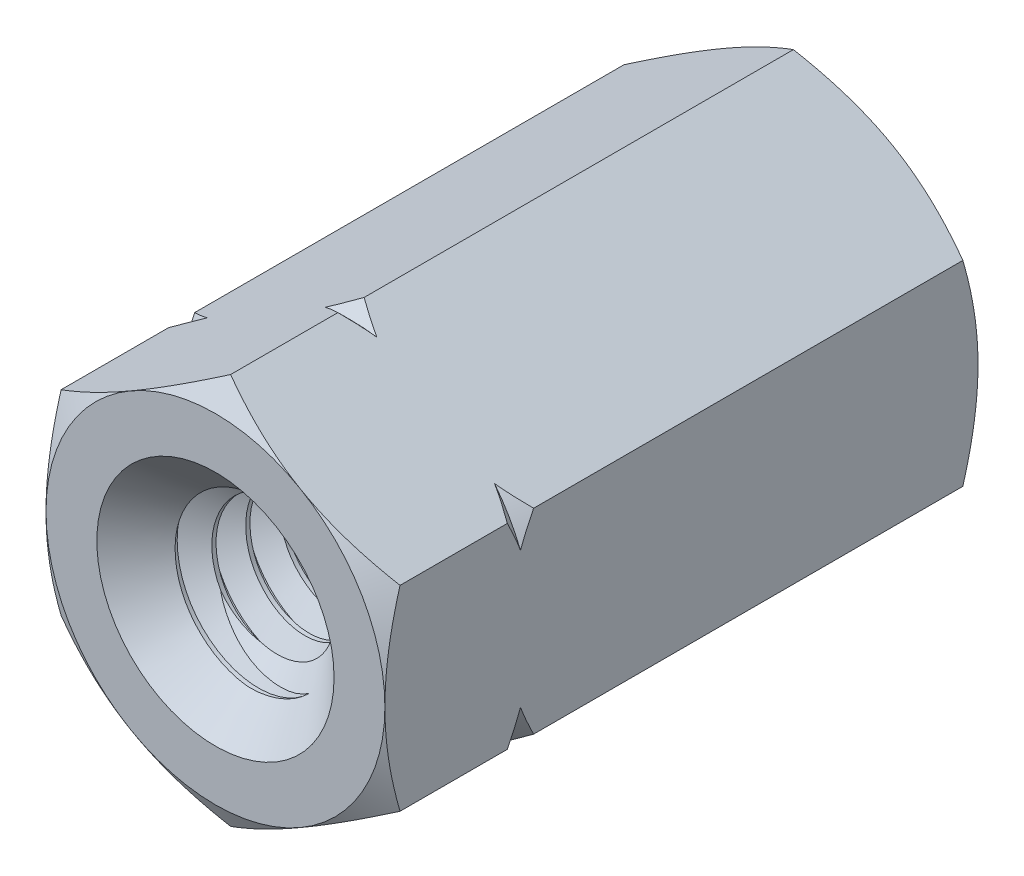
SolidWorks part; units mm, degrees
ref_plane "Front Plane" through (0, 0, 0) normal (0, 0, 1) x (1, 0, 0)
ref_plane "Top Plane" through (0, 0, 0) normal (0, 1, 0) x (1, 0, 0)
ref_plane "Right Plane" through (0, 0, 0) normal (1, 0, 0) x (0, 0, -1)
sketch "Sketch1" plane through (0, 0, 0) normal (0, 0, 1) x (1, 0, 0)
  line L0 (0, 0) -> (-2.2451, -2.2451) construction
  line L1 (6.35, 3.6662) -> (0, 7.3323)
  line L2 (0, 7.3323) -> (-6.35, 3.6662)
  line L3 (-6.35, 3.6662) -> (-6.35, -3.6662)
  line L4 (-6.35, -3.6662) -> (0, -7.3323)
  line L5 (0, -7.3323) -> (6.35, -3.6662)
  line L6 (6.35, -3.6662) -> (6.35, 3.6662)
  circle A1 centre (0, 0) radius 6.35 construction
  circle A2 centre (0, 0) radius 3.175 construction
  point P2 (-2.2451, -2.2451)
  dimension "Thread Size" = 6.35
  dimension "Width" = 12.7
  dimension "D1" = 45
sketch "Sketch2" plane through (0, 0, 0) normal (1, 0, 0) x (0, 0, -1)
  line L0 (-11.1125, 0) -> (11.1125, 0) construction
  line L1 (-11.1125, 3.175) -> (11.1125, 3.175) construction
  line L2 (11.1125, 3.175) -> (11.1125, 0) construction
  line L3 (-11.1125, 3.175) -> (-11.1125, 0) construction
  line L4 (-11.1125, 6.35) -> (11.1125, 6.35) construction
  line L5 (0, 3.175) -> (0, -3.175) construction
  line L6 (-11.0331, -3.3125) -> (-12.3031, -3.3125) construction
  line L7 (-12.3031, -3.3125) -> (-11.6681, -2.2126) construction
  line L8 (-11.6681, -2.2126) -> (-11.0331, -3.3125) construction
  line L9 (-11.6681, -2.2126) -> (-11.6681, -2.3501) construction
  line L10 (-11.7475, -2.3501) -> (-11.5888, -2.3501) construction
  line L11 (-11.6681, -3.175) -> (-11.6681, -3.3125) construction
  line L12 (-11.1125, -3.175) -> (-12.2238, -3.175) construction
  line L13 (-12.2634, -3.2437) -> (-11.0728, -3.2437) construction
  line L14 (-11.1125, 0) -> (-11.1125, -3.175) construction
  point P2 (-11.6681, -3.2437)
  point P7 (0, 3.175)
  point P22 (-6.0325, 0)
  point P26 (0, 6.35)
  point P27 (-11.7475, -2.3501)
  dimension "Length" = 22.225
  dimension "Pitch" = 1.27
  dimension "D1" = 0.1588
  dimension "Notch" = 5.08
sketch "Sketch3" plane through (0, 0, 0) normal (0, 0, 1) x (1, 0, 0)
  line L0 (6.35, -3.6662) -> (6.35, 3.6662) construction
  line L1 (0, -7.3323) -> (6.35, -3.6662) construction
  line L2 (-6.35, -3.6662) -> (0, -7.3323) construction
  line L3 (-6.35, 3.6662) -> (-6.35, -3.6662) construction
  line L4 (0, 7.3323) -> (-6.35, 3.6662) construction
  line L5 (6.35, 3.6662) -> (0, 7.3323) construction
  line L6 (6.35, -3.6662) -> (6.35, 3.6662)
  line L7 (0, -7.3323) -> (6.35, -3.6662)
  line L8 (-6.35, -3.6662) -> (0, -7.3323)
  line L9 (-6.35, 3.6662) -> (-6.35, -3.6662)
  line L10 (0, 7.3323) -> (-6.35, 3.6662)
  line L11 (6.35, 3.6662) -> (0, 7.3323)
  circle A0 centre (0, 0) radius 3.175 construction
  circle A1 centre (0, 0) radius 3.175
extrude "Boss-Extrude1" add sketch "Sketch3" along normal up to vertex (11.1125 mm away) and the other way up to vertex (11.1125 mm away) up to point (0, 0, 11.1125) other way up to point (0, 0, -11.1125)
sketch "Sketch4" plane through (0, 0, 0) normal (1, 0, 0) x (0, 0, -1)
  line L0 (-11.1125, 6.35) -> (11.1125, 6.35) construction
  line L1 (-11.1125, 6.35) -> (-10.5453, 7.3323)
  line L2 (-11.1125, 7.3323) -> (11.1125, 7.3323) construction
  line L3 (-10.5453, 7.3323) -> (-6.5237, 7.3323)
  line L4 (-6.5237, 7.3323) -> (-6.0325, 6.8412)
  line L5 (-6.0325, 6.8412) -> (-5.5413, 7.3323)
  line L6 (-5.5413, 7.3323) -> (10.5453, 7.3323)
  line L7 (10.5453, 7.3323) -> (11.1125, 6.35)
  line L9 (-11.1125, 3.6662) -> (-11.1125, 7.3323) construction
  line L12 (-11.1125, 0) -> (11.1125, 0) construction
  line L14 (-11.1125, 6.35) -> (-11.1125, 8.3147)
  line L15 (-11.1125, 8.3147) -> (11.1125, 8.3147)
  line L16 (11.1125, 8.3147) -> (11.1125, 6.35)
  line L17 (-10.8289, 6.8412) -> (-6.0325, 6.8412) construction
  dimension "D1" = 30
  dimension "D2" = 90
revolve "Cut-Revolve1" cut sketch "Sketch4" angle 360 about L12
chamfer "Chamfer1" distance 1.27 angle 45 2 edges at (3.175, 0, -11.1125) (3.175, 0, 11.1125)
sketch "Sketch5" plane through (0, 0, 11.1125) normal (0, 0, 1) x (1, 0, 0)
  circle A0 centre (0, 0) radius 3.175
curve "Helix/Spiral1" pitch 1.27 height 23.495 turns 18.5
sketch "Sketch6" plane through (0, 0, 0) normal (1, 0, 0) x (0, 0, -1)
  line L0 (-11.5888, -2.3501) -> (-11.7475, -2.3501)
  line L1 (-11.7475, -2.3501) -> (-12.2634, -3.2437)
  line L2 (-12.2634, -3.2437) -> (-11.0728, -3.2437)
  line L3 (-11.0728, -3.2437) -> (-11.5888, -2.3501)
sweep "Sweep1" add profiles "Sketch6" path "Helix/Spiral1"
sketch "Sketch7" plane through (0, 0, 11.1125) normal (0, 0, 1) x (1, 0, 0)
  circle A0 centre (0, 0) radius 4.445 construction
  circle A1 centre (0, 0) radius 4.445
extrude "Cut-Extrude1" cut sketch "Sketch7" against normal through all draft 45 and the other way through all
sketch "Sketch8" plane through (0, 0, -11.1125) normal (0, 0, -1) x (-1, 0, 0)
  circle A0 centre (0, 0) radius 4.445
  circle A1 centre (0, 0) radius 4.445 construction
extrude "Cut-Extrude2" cut sketch "Sketch8" against normal through all draft 45 and the other way through all
equation "\"D1@Sketch2\"=\"Pitch@Sketch2\"/8"
equation "\"D1@Chamfer1\"=\"Pitch@Sketch2\""
equation "\"D4@Helix/Spiral1\"=\"Pitch@Sketch2\""
equation "\"D3@Helix/Spiral1\"=\"Length@Sketch2\"+\"Pitch@Sketch2\""
equation "\"Notch@Sketch2\"=\"Width@Sketch1\"/2.5"
